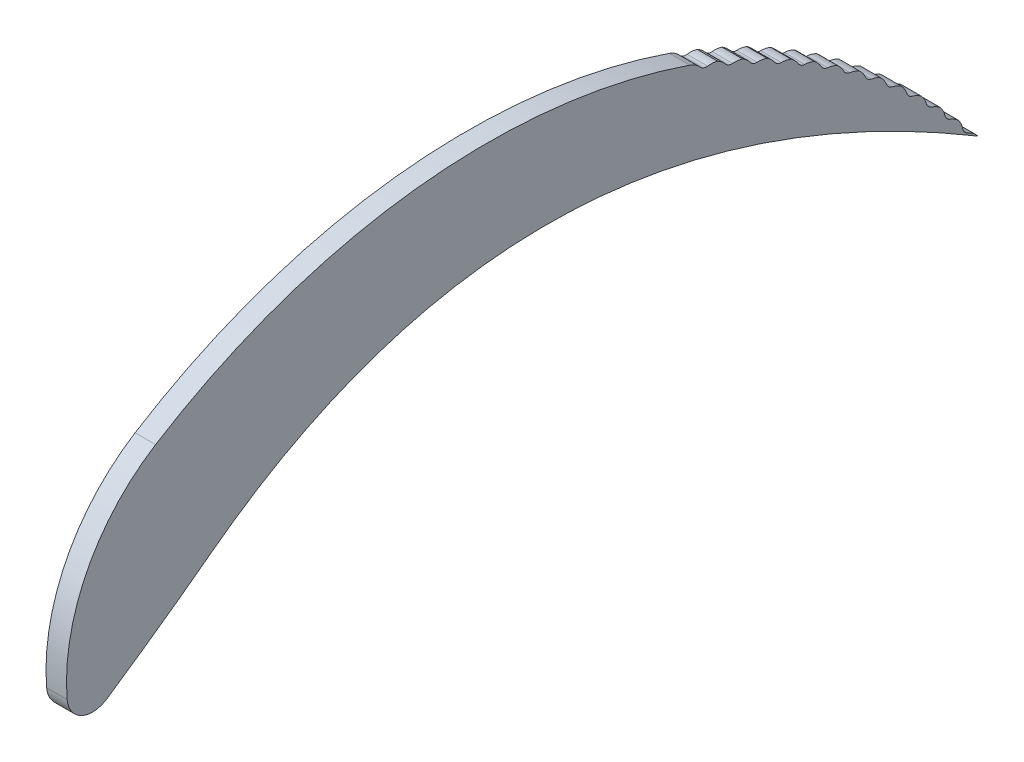
SolidWorks part; units mm, degrees
ref_plane "Front Plane" through (0, 0, 0) normal (0, 0, 1) x (1, 0, 0)
ref_plane "Top Plane" through (0, 0, 0) normal (0, 1, 0) x (1, 0, 0)
ref_plane "Right Plane" through (0, 0, 0) normal (1, 0, 0) x (0, 0, -1)
sketch "Sketch1" plane through (0, 0, 0) normal (1, 0, 0) x (0, 0, -1)
  line L1 (-63.5, 38.1) -> (63.5, 38.1) construction
  line L2 (-63.5, 38.1) -> (-63.5, -38.1) construction
  line L3 (-63.5, -38.1) -> (63.5, -38.1) construction
  line L4 (63.5, 38.1) -> (63.5, -38.1) construction
  arc A1 (-43.3811, 12.0309) -> (58.5764, -5.8357) centre (-2.2989, -53.3783) cw
  arc A2 (-43.3811, 12.0309) -> (-54.3506, -9.869) centre (-30.8293, -7.9534) ccw
  arc A5 (-49.4144, -12.246) -> (-36.4003, -2.9638) centre (-211.1097, 228.2225) ccw
  arc A6 (-54.3506, -9.869) -> (-49.4144, -12.246) centre (-51.1861, -9.6113) ccw
  spline S0 degree 2 poles (-36.4003, -2.9638) (3.4568, 27.1566) (58.5764, -5.8357) knots 0 0 0 1 1 1
  point P0 (0, 0)
  point P7 (0, 38.1)
  point P9 (63.5, 0)
  point P14 (-36.4003, -2.9638)
  dimension "D3" = 3.175
  dimension "D4" = 101.6
  dimension "D1" = 76.2
  dimension "D2" = 127
extrude "Boss-Extrude1" add sketch "Sketch1" along normal blind 2.54
sketch "Sketch2" plane through (2.54, 0, 0) normal (1, 0, 0) x (0, 0, -1)
  line L0 (-31.0198, -123.9853) -> (24.5396, 17.8309) construction
  line L1 (-31.0198, -123.9853) -> (28.178, 16.8836) construction
  circle A0 centre (24.9132, 19.4623) radius 1.0199
  circle A2 centre (27.7061, 18.3418) radius 1.0199
  arc A4 (58.5764, -5.8357) -> (-43.3811, 12.0309) centre (-2.2989, -53.3783) ccw
  arc A5 (-43.3811, 12.0309) -> (-54.3506, -9.869) centre (-30.8293, -7.9534) ccw
  arc A6 (-54.3506, -9.869) -> (-49.4144, -12.246) centre (-51.1861, -9.6113) ccw
  arc A7 (-49.4144, -12.246) -> (-36.4003, -2.9638) centre (-211.1097, 228.2225) ccw
  arc A8 (58.5764, -5.8357) -> (-43.3811, 12.0309) centre (-2.2989, -53.3783) ccw
  arc A9 (-43.3811, 12.0309) -> (-54.3506, -9.869) centre (-30.8293, -7.9534) ccw
  arc A10 (-54.3506, -9.869) -> (-49.4144, -12.246) centre (-51.1861, -9.6113) ccw
  arc A11 (-49.4144, -12.246) -> (-36.4003, -2.9638) centre (-211.1097, 228.2225) ccw
  circle A12 centre (30.4764, 17.1669) radius 1.0199
  circle A14 centre (33.2233, 15.9381) radius 1.0199
  circle A16 centre (35.9457, 14.6558) radius 1.0199
  circle A18 centre (38.6424, 13.3206) radius 1.0199
  circle A20 centre (41.3126, 11.9329) radius 1.0199
  circle A21 centre (33.7269, 14.0531) radius 0.8276
  circle A22 centre (43.9551, 10.4933) radius 1.0199
  circle A23 centre (35.038, 13.336) radius 0.8276
  circle A24 centre (46.569, 9.0023) radius 1.0199
  circle A25 centre (36.3349, 12.5935) radius 0.8276
  circle A26 centre (49.1533, 7.4605) radius 1.0199
  circle A27 centre (37.6171, 11.8257) radius 0.8276
  circle A28 centre (51.7069, 5.8686) radius 1.0199
  circle A29 centre (38.8839, 11.033) radius 0.8276
  circle A30 centre (54.2289, 4.227) radius 1.0199
  circle A31 centre (40.1351, 10.2157) radius 0.8276
  circle A32 centre (56.7184, 2.5364) radius 1.0199
  circle A33 centre (41.37, 9.3742) radius 0.8276
  circle A34 centre (59.1743, 0.7975) radius 1.0199
  circle A35 centre (42.5883, 8.5086) radius 0.8276
  circle A36 centre (61.5958, -0.989) radius 1.0199
  circle A37 centre (43.7894, 7.6194) radius 0.8276
  circle A38 centre (63.9819, -2.8226) radius 1.0199
  circle A39 centre (44.9728, 6.7069) radius 0.8276
  circle A40 centre (66.3317, -4.7024) radius 1.0199
  circle A41 centre (46.1383, 5.7714) radius 0.8276
  circle A42 centre (68.6444, -6.6278) radius 1.0199
  circle A43 centre (47.2852, 4.8133) radius 0.8276
  circle A44 centre (70.9189, -8.598) radius 1.0199
  circle A45 centre (48.4131, 3.833) radius 0.8276
  circle A46 centre (73.1545, -10.6123) radius 1.0199
  circle A47 centre (49.5217, 2.8308) radius 0.8276
  circle A48 centre (75.3504, -12.6699) radius 1.0199
  circle A49 centre (50.6105, 1.8072) radius 0.8276
  circle A50 centre (77.5056, -14.77) radius 1.0199
  circle A51 centre (51.6791, 0.7625) radius 0.8276
  circle A52 centre (79.6193, -16.9119) radius 1.0199
  circle A53 centre (52.727, -0.303) radius 0.8276
  circle A54 centre (81.6908, -19.0946) radius 1.0199
  circle A55 centre (53.754, -1.3887) radius 0.8276
  circle A56 centre (83.7192, -21.3174) radius 1.0199
  circle A57 centre (54.7595, -2.4942) radius 0.8276
  circle A58 centre (85.7038, -23.5795) radius 1.0199
  circle A59 centre (55.7432, -3.6192) radius 0.8276
  circle A60 centre (87.6438, -25.8799) radius 1.0199
  circle A61 centre (56.7047, -4.7633) radius 0.8276
  circle A62 centre (89.5385, -28.2177) radius 1.0199
  circle A63 centre (57.6437, -5.9259) radius 0.8276
  parabola Q1 (-36.4003, -2.9638) -> (58.5764, -5.8357) focus (-2.9253, -21.8548) apex (-10.5254, 9.5732)
  parabola Q2 (-36.4003, -2.9638) -> (58.5764, -5.8357) focus (-2.9253, -21.8548) apex (-10.5254, 9.5732)
  point P4 (25.238, 19.423)
  point P7 (24.8796, 19.5569)
  point P10 (26.3008, 18.9951)
  point P20 (24.5396, 17.8309)
  point P21 (26.5883, 17.3283)
  point P22 (28.178, 16.8836)
  point P23 (27.7061, 18.3418)
  arc M9 (58.5764, -5.8357) -> (-43.3811, 12.0309) centre (-2.2989, -53.3783) ccw
  dimension "D4" = 1.4
  dimension "D1" = 0
  dimension "D3" = 28
extrude "Cut-Extrude1" cut sketch "Sketch2" against normal blind 2.54 contours A0 M9
pattern_circular "CirPattern1" count 27 every 2.5 about axis through (0, -53.3783, 2.2989) along (1, 0, 0) of "Cut-Extrude1"
fillet "Fillet1" radius 3.048 26 edges at (1.27, -4.9106, -57.8425) (1.27, -3.5589, -56.7276) (1.27, -2.3334, -55.6711) (1.27, -1.0316, -54.4983) (1.27, 0.1466, -53.3894) (1.27, 1.3961, -52.1609) (1.27, 2.5247, -51.0017) (1.27, 3.7194, -49.7199) (1.27, 4.7965, -48.5125) (1.27, 5.9341, -47.1798) (1.27, 6.9575, -45.9266) (1.27, 8.0359, -44.5455) (1.27, 9.0036, -43.2489) (1.27, 10.0208, -41.8221) (1.27, 10.931, -40.4845) (1.27, 11.885, -39.0147) (1.27, 12.736, -37.6386) (1.27, 13.6249, -36.1286) (1.27, 14.4151, -34.7167) (1.27, 15.2373, -33.1694) (1.27, 15.9652, -31.7244) (1.27, 16.7191, -30.1427) (1.27, 17.3833, -28.6673) (1.27, 18.0675, -27.0542) (1.27, 18.6666, -25.5513) (1.27, 19.2799, -23.9098)
